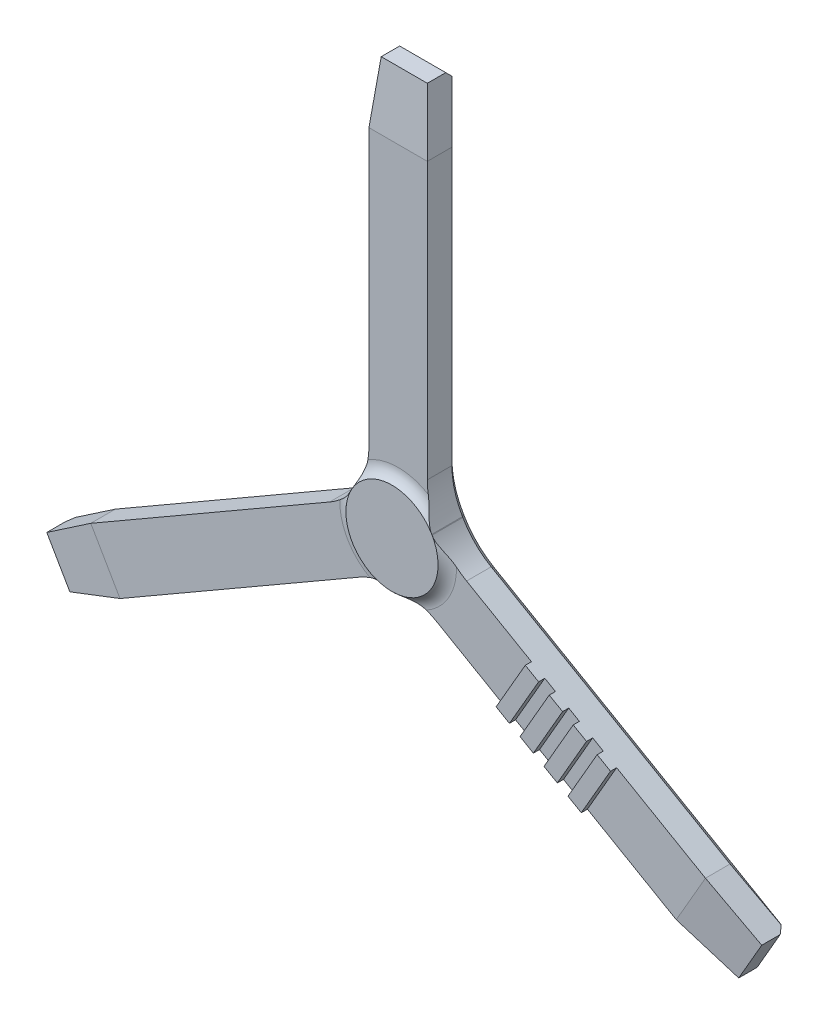
SolidWorks part; units mm, degrees
ref_plane "Front Plane" through (0, 0, 0) normal (0, 0, 1) x (1, 0, 0)
ref_plane "Top Plane" through (0, 0, 0) normal (0, 1, 0) x (1, 0, 0)
ref_plane "Right Plane" through (0, 0, 0) normal (1, 0, 0) x (0, 0, -1)
sketch "Sketch1" plane through (0, 0, 0) normal (0, 0, 1) x (1, 0, 0)
  line L0 (-1.9, 24) -> (1.9, 24) construction
  line L1 (0, 0) -> (0, 24) construction
  line L2 (-1.9, 24) -> (-1.9, 26)
  line L3 (-1.9, 26) -> (1.9, 26)
  line L4 (1.9, 26) -> (1.9, 24)
  line L5 (23.4667, -11.3546) -> (21.5667, -14.6454)
  line L6 (21.5667, -14.6454) -> (19.8346, -13.6454)
  line L7 (21.7346, -10.3546) -> (23.4667, -11.3546)
  line L8 (-21.5667, -14.6454) -> (-23.4667, -11.3546)
  line L9 (-23.4667, -11.3546) -> (-21.7346, -10.3546)
  line L10 (-19.8346, -13.6454) -> (-21.5667, -14.6454)
  line L11 (0, 0) -> (1.9, 24) construction
  line L12 (0, 0) -> (19.8346, -13.6454) construction
  line L13 (-1.9, 24) -> (-1.9, 1.097)
  line L14 (-1.9, 1.097) -> (-21.7346, -10.3546)
  line L15 (-19.8346, -13.6454) -> (0, -2.1939)
  line L16 (0, -2.1939) -> (19.8346, -13.6454)
  line L17 (21.7346, -10.3546) -> (1.9, 1.097)
  line L18 (1.9, 1.097) -> (1.9, 24)
  circle A0 centre (0, 0) radius 24 construction
  dimension "D1" = 48
  dimension "D2" = 3.8
  dimension "D3" = 2
  dimension "D4" = 120
  dimension "D5" = 24.0751
  dimension "D6" = 3
extrude "Boss-Extrude1" add sketch "Sketch1" along normal blind 2 contours L18 A0 L13 L14 L15 L16 L17 region at (0, 0, 0)
chamfer "Chamfer1" distance 4 distance2 0.4 3 edges at (22.5167, -13, 2) (-22.5167, -13, 2) (0, 26, 2) first distance on face at (0, 0, 2)
chamfer "Chamfer2" distance 0.4 distance2 4 3 edges at (23.4667, -11.3546, 0.8) (-1.9, 26, 0.8) (-21.5667, -14.6454, 0.8) first distance on face at (22.5167, -13, 0.8) first distance on face at (0, 26, 0.8) first distance on face at (-22.5167, -13, 0.8)
chamfer "Chamfer3" distance 4 distance2 0.4 3 edges at (1.9, 26, 0.8) (21.5667, -14.6454, 0.8) (-23.4667, -11.3546, 0.8) first distance on face at (1.9, 15.2388, 1.12) first distance on face at (12.2472, -9.2648, 1.12) first distance on face at (-14.1472, -5.9739, 1.12)
sketch "Sketch2" plane through (0, 0, 0) normal (0, 0, -1) x (-1, 0, 0)
  circle A0 centre (0, 0) radius 3
  dimension "D1" = 6
extrude "Boss-Extrude2" add sketch "Sketch2" against normal blind 2.4
fillet "Fillet1" radius 5 6 edges at (1.9, 2.3216, 1) (2.9606, 0.4846, 1) (1.0606, -2.8063, 1) (-1.0606, -2.8063, 1) (-2.9606, 0.4846, 1) (-1.9, 2.3216, 1)
fillet "Fillet2" radius 1 3 edges at (0, 3, 2) (2.5981, -1.5, 2) (-2.5981, -1.5, 2)
chamfer "Chamfer4" distance 0.4 angle 45 18 edges at (22.5167, -13, 0) (-22.5167, -13, 0) (0, 26, 0) (12.2293, -4.8667, 0) (3.4082, 0.4282, 0) (2.5981, 1.5, 0) (2.0749, 2.7374, 0) (1.9, 13.0242, 0) (-12.2293, -4.8667, 0) (-3.4082, 0.4282, 0) (-2.5981, 1.5, 0) (-2.0749, 2.7374, 0) (-1.9, 13.0242, 0) (10.3293, -8.1576, 0) (1.3332, -3.1657, 0) (0, -3, 0) (-1.3332, -3.1657, 0) (-10.3293, -8.1576, 0)
sketch "Sketch3" plane through (0, 0, 2) normal (0, 0, 1) x (1, 0, 0)
  line L0 (12.2293, -4.8667) -> (10.3293, -8.1576) construction
  line L3 (20.0026, -9.3546) -> (4.4561, -0.3788) construction
  line L5 (2.5561, -3.6697) -> (18.1026, -12.6454) construction
  line L7 (11.7963, -4.6167) -> (9.8963, -7.9076)
  line L8 (11.7963, -4.6167) -> (12.6623, -5.1167)
  line L9 (9.8963, -7.9076) -> (10.7623, -8.4076)
  line L10 (12.6623, -5.1167) -> (10.7623, -8.4076)
  line L11 (11.7963, -4.6167) -> (10.7623, -8.4076) construction
  line L12 (9.8963, -7.9076) -> (12.6623, -5.1167) construction
  line L13 (13.3551, -5.5167) -> (14.2212, -6.0167)
  line L14 (13.3551, -5.5167) -> (11.4551, -8.8076)
  line L15 (14.2212, -6.0167) -> (12.3212, -9.3076)
  line L16 (11.4551, -8.8076) -> (12.3212, -9.3076)
  line L29 (10.2375, -3.7167) -> (11.1035, -4.2167)
  line L30 (10.2375, -3.7167) -> (8.3375, -7.0076)
  line L31 (11.1035, -4.2167) -> (9.2035, -7.5076)
  line L32 (8.3375, -7.0076) -> (9.2035, -7.5076)
  line L33 (8.6786, -2.8167) -> (9.5446, -3.3167)
  line L34 (8.6786, -2.8167) -> (6.7786, -6.1076)
  line L35 (9.5446, -3.3167) -> (7.6446, -6.6076)
  line L36 (6.7786, -6.1076) -> (7.6446, -6.6076)
  line L465 (18.0317, -8.2167) -> (18.8977, -8.7167) [skipped]
  line L466 (18.0317, -8.2167) -> (16.1317, -11.5076) [skipped]
  line L467 (18.8977, -8.7167) -> (16.9977, -12.0076) [skipped]
  line L468 (16.1317, -11.5076) -> (16.9977, -12.0076) [skipped]
  line L469 (5.5609, -1.0167) -> (6.4269, -1.5167) [skipped]
  line L470 (5.5609, -1.0167) -> (3.6609, -4.3076) [skipped]
  line L471 (6.4269, -1.5167) -> (4.5269, -4.8076) [skipped]
  line L472 (3.6609, -4.3076) -> (4.5269, -4.8076) [skipped]
  line L473 (16.4728, -7.3167) -> (17.3389, -7.8167) [skipped]
  line L474 (16.4728, -7.3167) -> (14.5728, -10.6076) [skipped]
  line L475 (17.3389, -7.8167) -> (15.4389, -11.1076) [skipped]
  line L476 (14.5728, -10.6076) -> (15.4389, -11.1076) [skipped]
  line L477 (7.1198, -1.9167) -> (7.9858, -2.4167) [skipped]
  line L478 (7.1198, -1.9167) -> (5.2198, -5.2076) [skipped]
  line L479 (7.9858, -2.4167) -> (6.0858, -5.7076) [skipped]
  line L480 (5.2198, -5.2076) -> (6.0858, -5.7076) [skipped]
  line L481 (14.914, -6.4167) -> (15.78, -6.9167) [skipped]
  line L482 (14.914, -6.4167) -> (13.014, -9.7076) [skipped]
  line L483 (15.78, -6.9167) -> (13.88, -10.2076) [skipped]
  line L484 (13.014, -9.7076) -> (13.88, -10.2076) [skipped]
  point P7 (11.2793, -6.5121)
  dimension "D1" = 1
extrude "Boss-Extrude3" add sketch "Sketch3" along normal blind 0.4
